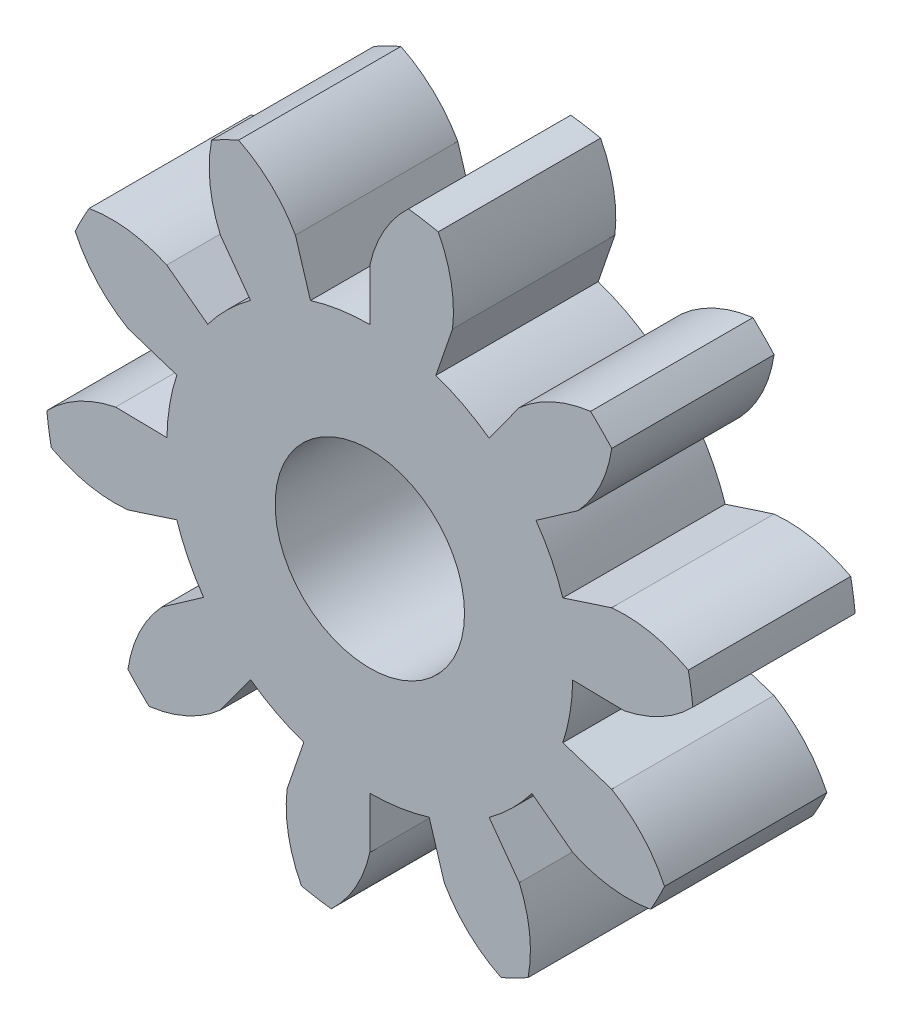
SolidWorks part; units mm, degrees
ref_plane "Plan de face" through (0, 0, 0) normal (0, 0, 1) x (1, 0, 0)
ref_plane "Plan de dessus" through (0, 0, 0) normal (0, 1, 0) x (1, 0, 0)
ref_plane "Plan de droite" through (0, 0, 0) normal (1, 0, 0) x (0, 0, -1)
sketch "Esquisse1" plane through (0, 0, 0) normal (0, 0, 1) x (1, 0, 0)
  circle A0 centre (0, 0) radius 5
  circle A1 centre (0, 0) radius 6
  circle A2 centre (0, 0) radius 3.75
  circle A3 centre (0, 0) radius 4
  circle A4 centre (0, 0) radius 4.6985
  dimension "Pitch Circle" = 10
  dimension "Addendum Circle" = 12
  dimension "Root Circle" = 7.5
  dimension "Clearence Circle" = 8
  dimension "Base Circle" = 9.3969
sketch "Involute" plane through (0, 0, 0) normal (0, 0, 1) x (1, 0, 0)
  line L0 (0, 0) -> (0, 4.6985)
  line L1 (0, 0) -> (2.3492, 4.069) construction
  line L2 (0, 0) -> (4.069, 2.3492) construction
  line L3 (0, 0) -> (4.6985, 0) construction
  line L4 (4.6985, 0) -> (4.6985, 7.3803) construction
  line L5 (4.069, 2.3492) -> (1.6089, 6.6103) construction
  line L6 (2.3492, 4.069) -> (0.2187, 5.299) construction
  line L7 (0, 0) -> (1.5451, 4.7553) construction
  line L8 (2.9389, 4.0451) -> (0, 0)
  line L9 (0.8247, 4.9315) -> (0, 0) construction
  circle A0 centre (0, 0) radius 4.6985 construction
  circle A1 centre (0, 0) radius 5 construction
  arc A2 (1.5451, 4.7553) -> (0.0861, 4.9993) centre (0, 0) ccw
  spline S0 degree 3 poles (0, 4.6985) (0.4133, 6.6226) (3.1129, 7.3828) (4.6985, 7.3803) knots 0 0 0 0 1 1 1 1
  spline S1 degree 3 poles (1.5287, 4.4428) (1.7639, 6.3967) (-0.5415, 7.994) (-2.0416, 8.5074) knots 0 0 0 0 1 1 1 1
  dimension "Involute Control" = 90
  dimension "Base Circle Quarter Circumference" = 7.3803
  dimension "D1" = 4.9202
  dimension "D2" = 2.4601
  dimension "Circular Pitch" = 36
  dimension "Involute Array" = 4
sketch "Esquisse4" plane through (0, 0, 0) normal (0, 0, 1) x (1, 0, 0)
  line L0 (0, 0) -> (0, 4.6985) construction
  line L1 (0, 4.6985) -> (0, 3.75)
  line L2 (1.5287, 4.4428) -> (1.2201, 3.546)
  arc A0 (0.7133, 5.9575) -> (1.2638, 5.8654) centre (0, 0) cw
  circle A1 centre (0, 0) radius 6 construction
  arc A2 (0, 3.75) -> (1.2201, 3.546) centre (0, 0) cw
  circle A3 centre (0, 0) radius 3.75 construction
  arc A4 (0, 4.6985) -> (0.7133, 5.9575) centre (2.387, 4.1776) cw
  arc A5 (1.2638, 5.8654) -> (1.5287, 4.4428) centre (-0.898, 4.727) cw
  spline S0 degree 3 poles (0, 4.6985) (0.4133, 6.6226) (3.1129, 7.3828) (4.6985, 7.3803) knots 0 0 0 0 1 1 1 1 construction
  spline S1 degree 3 poles (1.5287, 4.4428) (1.7639, 6.3967) (-0.5415, 7.994) (-2.0416, 8.5074) knots 0 0 0 0 1 1 1 1 construction
extrude "Boss.-Extru.1" add sketch "Esquisse4" along normal blind 3
ref_axis "Axe1" through (0, 0, 0) along (0, 0, 1)
pattern_circular "Répétition circulaire2" count 10 over 360 about axis through (0, 0, 0) along (0, 0, 1) of bodies 101
sketch "Esquisse5" plane through (0, 0, 0) normal (0, 0, 1) x (1, 0, 0)
  circle A0 centre (0, 0) radius 3.75 construction
  circle A1 centre (0, 0) radius 3.75
extrude "Boss.-Extru.2" add sketch "Esquisse5" along normal up to surface (3 mm away)
sketch "Esquisse6" plane through (0, 0, 3) normal (0, 0, 1) x (1, 0, 0)
  circle A0 centre (0, 0) radius 1.75
  dimension "D1" = 3.5
extrude "Enlèv. mat.-Extru.1" cut sketch "Esquisse6" against normal through all
equation "\"Module\"= 1"
equation "\"Nb de dents\"= 10"
equation "\"Pressure Angle\"= 20"
equation "\"Pitch Circle@Esquisse1\"= \"Module\" * \"Nb de dents\""
equation "\"Addendum Circle@Esquisse1\"= \"Pitch Circle@Esquisse1\" + ( \"Module\" * 2 )"
equation "\"Clearence Circle@Esquisse1\"= \"Pitch Circle@Esquisse1\" - ( \"Module\" * 2 )"
equation "\"Root Circle@Esquisse1\"= \"Pitch Circle@Esquisse1\" - ( ( \"Module\" * 1.25 ) * 2 )"
equation "\"Base Circle@Esquisse1\"= \"Pitch Circle@Esquisse1\" * cos ( \"Pressure Angle\" )"
equation "\"Base Circle Quarter Circumference@Involute\" = \"Base Circle@Esquisse1\" * pI / 4"
equation "\"D1@Involute\"=\"Base Circle Quarter Circumference@Involute\"/3*2"
equation "\"D2@Involute\"=\"Base Circle Quarter Circumference@Involute\"/3"
equation "\"Circular Pitch@Involute\"=360/\"Nb de dents\""
equation "\"D1@Répétition circulaire2\"= \"Nb de dents\""
